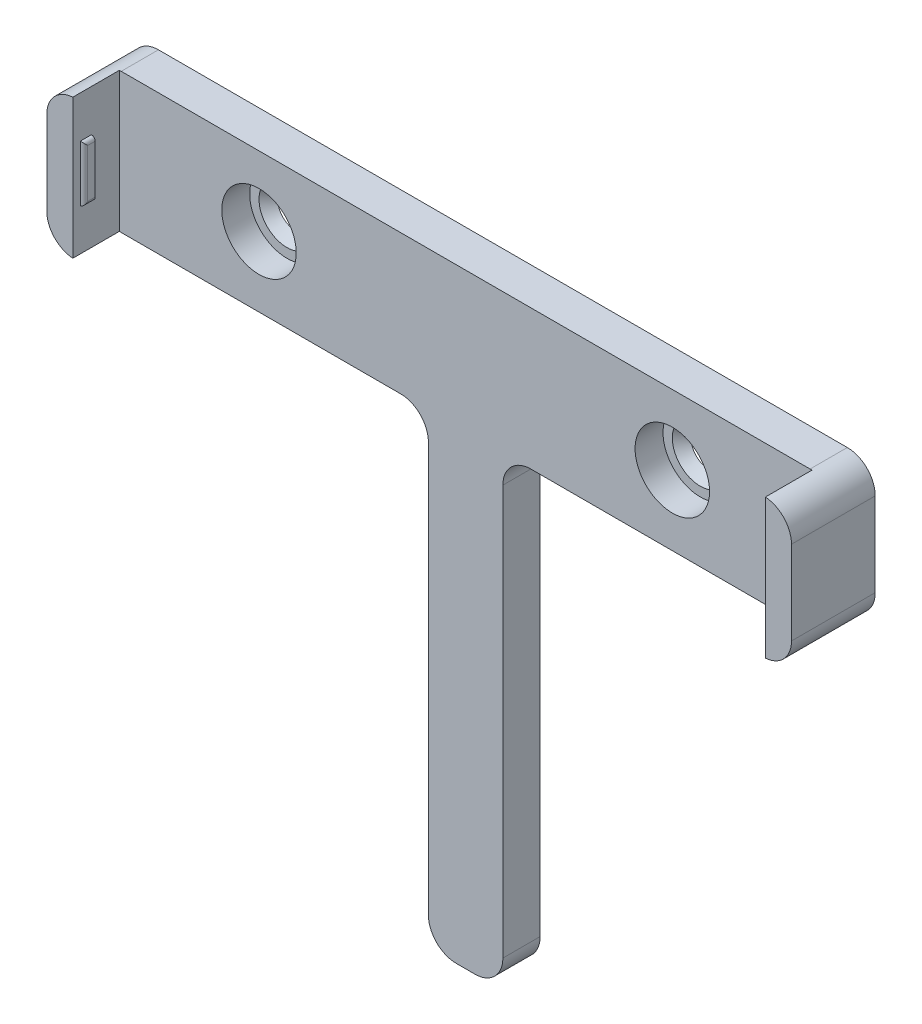
SolidWorks part; units mm, degrees
ref_plane "Front Plane" through (0, 0, 0) normal (0, 0, 1) x (1, 0, 0)
ref_plane "Top Plane" through (0, 0, 0) normal (0, 1, 0) x (1, 0, 0)
ref_plane "Right Plane" through (0, 0, 0) normal (1, 0, 0) x (0, 0, -1)
sketch "Sketch1" plane through (0, 0, 0) normal (0, 0, 1) x (1, 0, 0)
  line L1 (0, 0) -> (80, 0)
  line L2 (0, 0) -> (0, 15)
  line L3 (0, 15) -> (80, 15)
  line L4 (80, 0) -> (80, 15)
  dimension "D1" = 80
  dimension "D2" = 15
extrude "Boss-Extrude1" add sketch "Sketch1" along normal blind 4
sketch "Sketch2" plane through (0, 0, 4) normal (0, 0, 1) x (1, 0, 0)
  line L0 (0, 0) -> (80, 0) construction
  line L1 (0, 15) -> (2.8, 15)
  line L2 (0, 15) -> (0, 0)
  line L3 (0, 0) -> (2.8, 0)
  line L4 (2.8, 15) -> (2.8, 0)
  line L6 (80, 15) -> (77.2, 15)
  line L7 (80, 15) -> (80, 0)
  line L8 (80, 0) -> (77.2, 0)
  line L9 (77.2, 15) -> (77.2, 0)
  dimension "D1" = 2.8
  dimension "D2" = 2.8
extrude "Boss-Extrude2" add sketch "Sketch2" along normal blind 5
sketch "Sketch3" plane through (2.8, 0, 0) normal (1, 0, 0) x (0, 0, -1)
  line L0 (-9, 15) -> (-4, 15) construction
  line L1 (-8.2, 4.5) -> (-7, 4.5)
  line L2 (-8.2, 4.5) -> (-8.2, 10.5)
  line L3 (-8.2, 10.5) -> (-7, 10.5)
  line L4 (-7, 4.5) -> (-7, 10.5)
  line L5 (-9, 0) -> (-9, 15) construction
  dimension "D1" = 6
  dimension "D2" = 4.5
  dimension "D3" = 1.2
  dimension "D4" = 0.8
extrude "Boss-Extrude3" add sketch "Sketch3" along normal blind 0.4
sketch "Sketch4" plane through (77.2, 0, 0) normal (-1, 0, 0) x (0, 0, 1)
  line L0 (9, 15) -> (4, 15) construction
  line L1 (8.2, 10.5) -> (7, 10.5)
  line L2 (8.2, 10.5) -> (8.2, 4.5)
  line L3 (8.2, 4.5) -> (7, 4.5)
  line L4 (7, 10.5) -> (7, 4.5)
  line L5 (9, 15) -> (9, 0) construction
  dimension "D1" = 1.2
  dimension "D2" = 4.5
  dimension "D3" = 0.8
  dimension "D4" = 6
extrude "Boss-Extrude4" add sketch "Sketch4" along normal blind 0.4
fillet "Fillet1" radius 0.4 6 edges at (3.2, 10.5, 7.6) (3.2, 4.5, 7.6) (76.8, 10.5, 7.6) (76.8, 4.5, 7.6) (76.8, 7.5, 8.2) (3.2, 7.5, 8.2)
fillet "Fillet2" radius 3 4 edges at (80, 0, 4.5) (80, 15, 4.5) (0, 0, 4.5) (0, 15, 4.5)
sketch "Sketch5" plane through (0, 0, 0) normal (0, 0, 1) x (1, 0, 0)
  line L0 (40, 0) -> (40, -39.9859) construction
  line L1 (3, 0) -> (77, 0) construction
  line L3 (36, 0) -> (44, 0)
  line L4 (36, 0) -> (36, -50)
  line L5 (36, -50) -> (44, -50)
  line L6 (44, 0) -> (44, -50)
  dimension "D1" = 8
  dimension "D2" = 4
  dimension "D3" = 50
extrude "Boss-Extrude5" add sketch "Sketch5" along normal blind 4
fillet "Fillet3" radius 3 4 edges at (36, -50, 2) (44, -50, 2) (44, 0, 2) (36, 0, 2)
sketch "Sketch6" plane through (0, 0, 4) normal (0, 0, 1) x (1, 0, 0)
  line L0 (2.8, 7.5) -> (77.2, 7.5) construction
  line L1 (2.8, 0.0067) -> (2.8, 14.9933) construction
  line L2 (77.2, 14.9933) -> (77.2, 0.0067) construction
  circle A0 centre (17.8, 7.5) radius 4
  circle A1 centre (62.2, 7.5) radius 4
  dimension "D3" = 8
  dimension "D4" = 8
  dimension "D1" = 15
  dimension "D2" = 15
extrude "Cut-Extrude1" cut sketch "Sketch6" against normal blind 3
sketch "Sketch7" plane through (0, 0, 1) normal (0, 0, 1) x (1, 0, 0)
  circle A0 centre (17.8, 7.5) radius 2
  circle A1 centre (62.2, 7.5) radius 2
  dimension "D1" = 4
  dimension "D2" = 4
extrude "Cut-Extrude2" cut sketch "Sketch7" against normal blind 3
chamfer "Chamfer1" distance 1 angle 45 2 edges at (19.8, 7.5, 1) (64.2, 7.5, 1)
